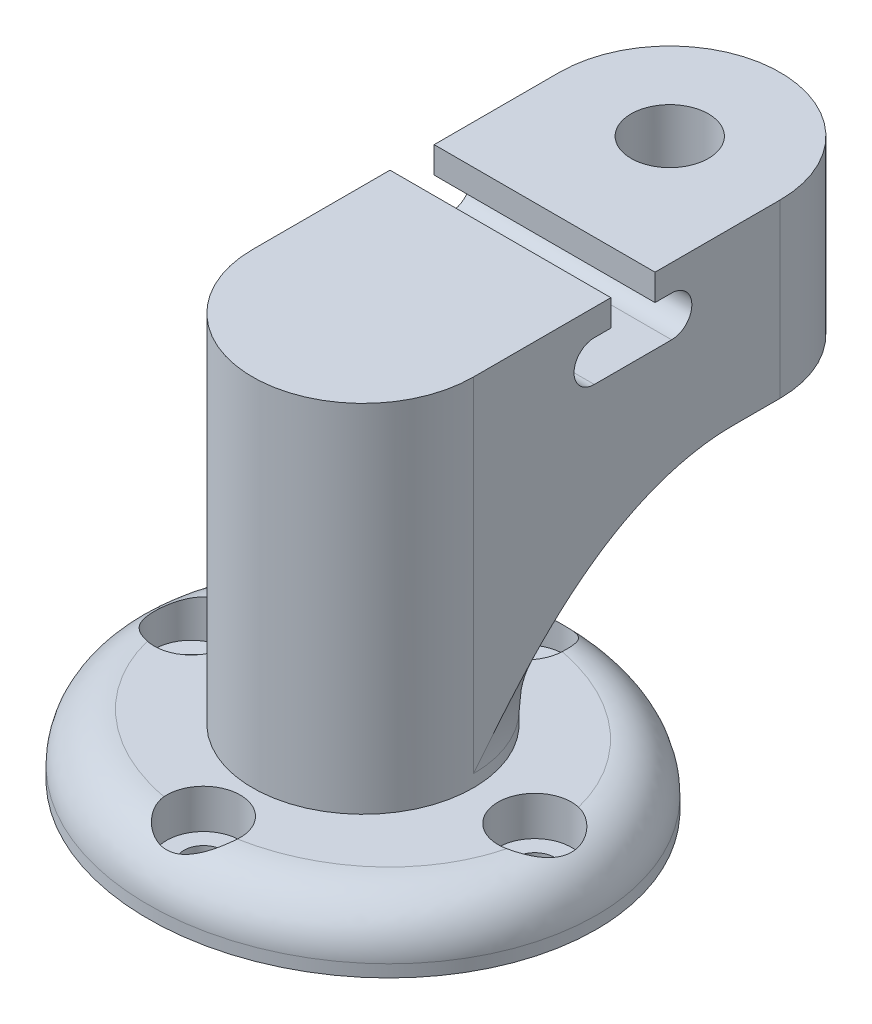
SolidWorks part; units mm, degrees
ref_plane "Front Plane" through (0, 0, 0) normal (0, 0, 1) x (1, 0, 0)
ref_plane "Top Plane" through (0, 0, 0) normal (0, 1, 0) x (1, 0, 0)
ref_plane "Right Plane" through (0, 0, 0) normal (1, 0, 0) x (0, 0, -1)
sketch "Sketch1" plane through (0, 0, 0) normal (0, 1, 0) x (1, 0, 0)
  circle A0 centre (0, 0) radius 9
  dimension "D1" = 18
extrude "Boss-Extrude1" add sketch "Sketch1" along normal blind 100
sketch "Sketch4" plane through (0, 100, 0) normal (0, 1, 0) x (1, 0, 0)
  line L0 (0, 0) -> (0, 25) construction
  line L5 (-9, 0) -> (-9, 25)
  line L6 (9, 0) -> (9, 25)
  arc A0 (-9, 0) -> (9, 0) centre (0, 0) ccw
  arc A1 (9, 25) -> (-9, 25) centre (0, 25) ccw
  point P2 (0, 12.5)
  dimension "D1" = 9
  dimension "D2" = 25
extrude "Boss-Extrude2" add sketch "Sketch4" along normal blind 14
sketch "Sketch5" plane through (0, 100, 0) normal (0, -1, 0) x (1, 0, 0)
  line L1 (-9, -25) -> (-9, 0) construction
  arc A0 (-9, -25) -> (9, -25) centre (0, -25) ccw construction
  circle A1 centre (0, -25) radius 5.15
  point P0 (0, -25)
  dimension "D3" = 10.3
  dimension "D1" = 0
  dimension "D2" = 9
extrude "Cut-Extrude2" cut sketch "Sketch5" against normal blind 8.8
sketch "Sketch6" plane through (0, 108.8, 0) normal (0, -1, 0) x (1, 0, 0)
  circle A0 centre (0, -25) radius 3.15
  point P0 (0, -25)
  dimension "D1" = 6.3
extrude "Cut-Extrude4" cut sketch "Sketch6" against normal up to surface (5.2 mm away) up to face at (0, 114, -12.5)
sketch "Sketch7" plane through (9, 0, 0) normal (1, 0, 0) x (0, 0, -1)
  line L0 (9.85, 110.2) -> (16.15, 110.2) construction
  line L1 (9.85, 111.85) -> (11.2, 111.85)
  line L2 (9.85, 108.55) -> (16.15, 108.55)
  line L3 (25, 114) -> (25, 100) construction
  line L4 (0, 114) -> (25, 114) construction
  line L5 (13, 110.2) -> (13, 114) construction
  line L6 (13, 114) -> (11.2, 114)
  line L7 (11.2, 114) -> (11.2, 111.85)
  line L8 (13, 114) -> (14.8, 114)
  line L9 (14.8, 114) -> (14.8, 111.85)
  line L10 (14.8, 111.85) -> (16.15, 111.85)
  arc A0 (9.85, 111.85) -> (9.85, 108.55) centre (9.85, 110.2) ccw
  arc A1 (16.15, 108.55) -> (16.15, 111.85) centre (16.15, 110.2) ccw
  point P2 (13, 110.2)
  dimension "D1" = 3.3
  dimension "D2" = 6.3
  dimension "D3" = 12
  dimension "D4" = 3.8
  dimension "D5" = 1.8
  dimension "D6" = 1.8
  dimension "D7" = 0
extrude "Cut-Extrude5" cut sketch "Sketch7" against normal up to surface (18 mm away) up to face at (-9, 107, -12.5)
sketch "Sketch8" plane through (0, 0, 0) normal (0, -1, 0) x (1, 0, 0)
  circle A0 centre (0, 0) radius 12.5
extrude "Cut-Extrude6" cut sketch "Sketch8" against normal blind 85
sketch "Sketch12" plane through (0, 85, 0) normal (0, -1, 0) x (1, 0, 0)
  ellipse E0 centre (0, 0) end of major axis (19, 0) minor radius 17.5
  dimension "D1" = 38
  dimension "D2" = 35
extrude "Boss-Extrude3" add sketch "Sketch12" along normal blind 5 contours E0
sketch "Sketch13" plane through (0, 80, 0) normal (0, -1, 0) x (-1, 0, 0)
  line L0 (19, 0) -> (-19, 0) construction
  line L1 (0, -17.5) -> (0, 17.5) construction
  circle A0 centre (14, 0) radius 1.6
  circle A1 centre (0, -13) radius 1.6
  circle A2 centre (-14, 0) radius 1.6
  circle A3 centre (0, 13.33) radius 1.6
  ellipse E0 centre (0, 0) end of major axis (-19, 0) minor radius 17.5 construction
  point P11 (0, -13)
  point P12 (0, 13.33)
  point P13 (14, 0)
  point P14 (-14, 0)
  dimension "D5" = 3.2
  dimension "D6" = 3.2
  dimension "D7" = 3.2
  dimension "D8" = 3.2
  dimension "D1" = 14
  dimension "D2" = 14
  dimension "D3" = 13.33
  dimension "D4" = 13
extrude "Cut-Extrude7" cut sketch "Sketch13" against normal up to surface (5 mm away) up to face at (0, 85, -9)
sketch "Sketch15" plane through (0, 85, 0) normal (0, 1, 0) x (1, 0, 0)
  circle A0 centre (14, 0) radius 3
  circle A1 centre (0, -13) radius 3
  circle A2 centre (-14, 0) radius 3
  circle A3 centre (0, 13.33) radius 3
  dimension "D1" = 6
  dimension "D2" = 6
  dimension "D3" = 6
  dimension "D4" = 6
extrude "Cut-Extrude8" cut sketch "Sketch15" against normal blind 3.2
fillet "Fillet1" radius 4 1 edges at (19, 85, 0)
fillet "Fillet2" radius 14 1 edges at (0, 100, -9) type face fillet first side face at (0, 100, -30.15) second side face at (0, 107, 0)
